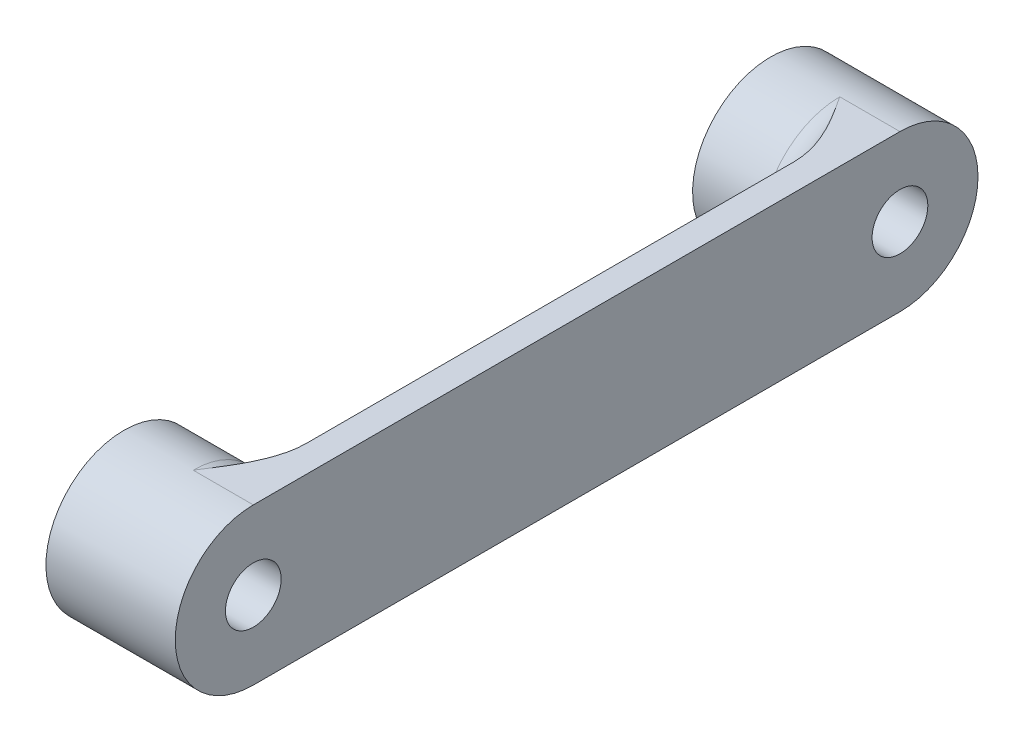
SolidWorks part; units mm, degrees
ref_plane "Front Plane" through (0, 0, 0) normal (0, 0, 1) x (1, 0, 0)
ref_plane "Top Plane" through (0, 0, 0) normal (0, 1, 0) x (1, 0, 0)
ref_plane "Right Plane" through (0, 0, 0) normal (1, 0, 0) x (0, 0, -1)
sketch "Sketch1" plane through (0, 0, 0) normal (1, 0, 0) x (0, 0, -1)
  line L0 (-29, 0) -> (29, 0)
  circle A0 centre (-29, 0) radius 2.5
  circle A1 centre (29, 0) radius 2.5
  circle A2 centre (-29, 0) radius 7
  circle A3 centre (29, 0) radius 7
  point P4 (0, 0)
  dimension "D1" = 5
  dimension "D3" = 14
  dimension "D2" = 58
extrude "Boss-Extrude1" add sketch "Sketch1" along normal blind 9.2 contours A2 A0 | A3 A1 region at (0, 0, 35.802) region at (0, 6.802, -29)
sketch "Sketch2" plane through (9.2, 0, 0) normal (1, 0, 0) x (0, 0, -1)
  line L0 (-29, 7) -> (29, 7)
  line L1 (29, -7) -> (-29, -7)
  circle A0 centre (29, 0) radius 7 construction
  circle A1 centre (-29, 0) radius 7 construction
  circle A2 centre (29, 0) radius 7
  circle A3 centre (-29, 0) radius 7
  circle A4 centre (29, 0) radius 2.5 construction
  circle A5 centre (-29, 0) radius 2.5 construction
  circle A6 centre (29, 0) radius 2.5
  circle A7 centre (-29, 0) radius 2.5
  circle M3 centre (-29, 0) radius 7
  circle M4 centre (-29, 0) radius 2.5
extrude "Boss-Extrude2" add sketch "Sketch2" along normal blind 2.4 contours M3 M4 | A2 L0 L1 M3 | A2 A6 region at (9.2, 0, 0) region at (9.2, 4.8097, 24.1903) region at (9.2, 4.8097, -33.8097)
fillet "Fillet1" radius 3 2 edges at (9.2, 0, 22) (9.2, 0, -22)
